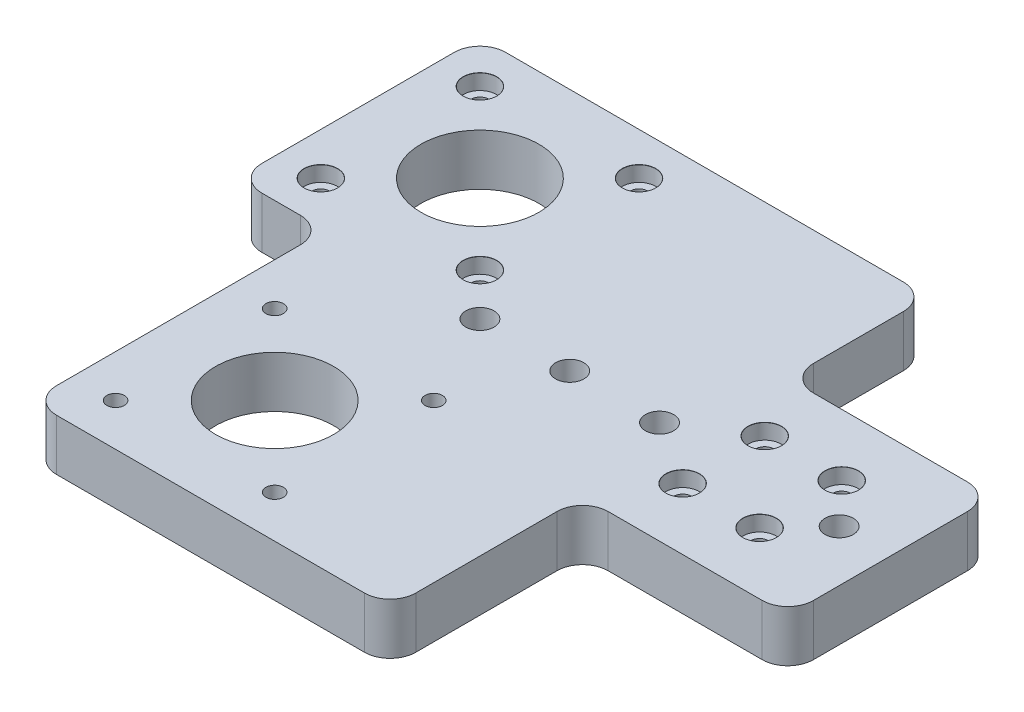
SolidWorks part; units mm, degrees
ref_plane "Front Plane" through (0, 0, 0) normal (0, 0, 1) x (1, 0, 0)
ref_plane "Top Plane" through (0, 0, 0) normal (0, 1, 0) x (1, 0, 0)
ref_plane "Right Plane" through (0, 0, 0) normal (1, 0, 0) x (0, 0, -1)
sketch "Sketch1" plane through (0, 0, 0) normal (0, 1, 0) x (1, 0, 0)
  line L0 (0, 0) -> (110, 0) construction
  line L1 (110, 0) -> (110, 20) construction
  line L2 (110, 20) -> (0, 20) construction
  line L3 (0, 20) -> (0, 0) construction
  line L4 (110, 30) -> (110, -10) construction
  line L5 (110, 30) -> (80, 30) construction
  line L6 (80, 30) -> (80, -10) construction
  line L7 (80, -10) -> (110, -10) construction
  line L8 (0, 67.5) -> (0, -47.5)
  line L16 (0, 67.5) -> (70, 67.5)
  line L18 (0, -47.5) -> (70, -47.5)
  line L19 (70, 67.5) -> (70, 30)
  line L22 (110, -10) -> (70, -10)
  line L23 (70, -10) -> (70, -47.5)
  line L24 (70, 30) -> (110, 30)
  line L25 (110, 30) -> (110, -10)
  point P8 (110, 10)
  point P13 (0, 10)
  dimension "D1" = 20
  dimension "D2" = 37.5
  dimension "D3" = 30
  dimension "D4" = 40
  dimension "D5" = 110
  dimension "D6" = 10
extrude "Boss-Extrude1" add sketch "Sketch1" along normal blind 10
fillet "Fillet1" radius 5 8 edges at (70, 5, -30) (110, 5, -30) (110, 5, 10) (70, 5, 10) (0, 5, 47.5) (0, 5, -67.5) (70, 5, -67.5) (70, 5, 47.5)
sketch "Sketch3" plane through (0, 10, 0) normal (0, 1, 0) x (1, 0, 0)
  line L0 (5, -47.5) -> (65, -47.5) construction
  line L1 (0, 62.5) -> (0, -42.5) construction
  circle A0 centre (23.75, -23.75) radius 11.5
  dimension "D3" = 23
  dimension "D1" = 23.75
  dimension "D2" = 23.75
extrude "Cut-Extrude1" cut sketch "Sketch3" against normal blind 10
sketch "Sketch4" plane through (0, 0, 0) normal (0, -1, 0) x (1, 0, 0)
  line L1 (39.25, 39.25) -> (8.25, 39.25)
  line L2 (39.25, 39.25) -> (39.25, 8.25)
  line L3 (39.25, 8.25) -> (8.25, 8.25)
  line L4 (8.25, 39.25) -> (8.25, 8.25)
  line L5 (39.25, 39.25) -> (8.25, 8.25) construction
  line L6 (39.25, 8.25) -> (8.25, 39.25) construction
  point P0 (23.75, 23.75)
  dimension "D1" = 31
hole_wizard "CBORE for M3 SHCS1" positions "Sketch5" profile "Sketch6" counterbore size "M3" standard "ANSI Metric" end condition through all
sketch "Sketch5" plane through (0, 0, 0) normal (0, -1, 0) x (-1, 0, 0)
  point P0 (-39.25, -8.25)
  point P3 (-8.25, -39.25)
  point P6 (-8.25, -8.25)
  point P9 (-39.25, -39.25)
sketch "Sketch6" plane through (39.25, 0, 8.25) normal (1, 0, 0) x (0, 0, -1)
  line L0 (0, 0) -> (0, 10)
  line L1 (0, 10) -> (1.7, 10)
  line L3 (1.7, 10) -> (1.7, 3)
  line L4 (3.25, 3) -> (1.7, 3)
  line L5 (3.25, 3) -> (3.25, 0.025)
  line L6 (3.25, 0.025) -> (3.275, 0)
  line L7 (3.275, 0) -> (0, 0)
  line L8 (-3.25, 0.025) -> (-3.275, 0) construction
  line L11 (0, -6.35) -> (0, 107.95) construction
  dimension "Thru Hole Dia." = 3.4
  dimension "Thru Hole Depth" = 10
  dimension "C'Bore Dia." = 6.5
  dimension "C'Bore Depth" = 3
  dimension "Near C'Sink Dia." = 6.55
  dimension "Near C'Sink Angle" = 90
sketch "Sketch7" plane through (0, 10, 0) normal (0, 1, 0) x (1, 0, 0)
  line L1 (92.5, 18) -> (77.5, 18)
  line L2 (92.5, 18) -> (92.5, 2)
  line L3 (92.5, 2) -> (77.5, 2)
  line L4 (77.5, 18) -> (77.5, 2)
  line L5 (92.5, 18) -> (77.5, 2) construction
  line L6 (92.5, 2) -> (77.5, 18) construction
  line L7 (110, 10) -> (0, 10)
  line L8 (0, 67.5) -> (0, -47.5) construction
  line L10 (110, 30) -> (110, -10) construction
  point P0 (85, 10)
  dimension "D1" = 15
  dimension "D2" = 16
  dimension "D3" = 25
hole_wizard "CBORE for M3 SHCS2" positions "Sketch8" profile "Sketch9" counterbore size "M3" standard "ANSI Metric" end condition through all
sketch "Sketch8" plane through (0, 10, 0) normal (0, 1, 0) x (1, 0, 0)
  point P0 (77.5, 18)
  point P3 (92.5, 18)
  point P6 (92.5, 2)
  point P9 (77.5, 2)
sketch "Sketch9" plane through (77.5, 10, -18) normal (1, 0, 0) x (0, 0, 1)
  line L0 (0, 0) -> (0, 10)
  line L1 (0, 10) -> (1.7, 10)
  line L3 (1.7, 10) -> (1.7, 3)
  line L4 (3.25, 3) -> (1.7, 3)
  line L5 (3.25, 3) -> (3.25, 0.025)
  line L6 (3.25, 0.025) -> (3.275, 0)
  line L7 (3.275, 0) -> (0, 0)
  line L8 (-3.25, 0.025) -> (-3.275, 0) construction
  line L11 (0, -6.35) -> (0, 107.95) construction
  dimension "Thru Hole Dia." = 3.4
  dimension "Thru Hole Depth" = 10
  dimension "C'Bore Dia." = 6.5
  dimension "C'Bore Depth" = 3
  dimension "Near C'Sink Dia." = 6.55
  dimension "Near C'Sink Angle" = 90
sketch "Sketch10" plane through (0, 0, 0) normal (0, -1, 0) x (1, 0, 0)
  line L0 (110, -10) -> (0, -10) construction
  line L1 (110, 5) -> (110, -25) construction
  line L2 (0, -62.5) -> (0, 42.5) construction
  point P6 (100, -10)
  point P7 (30, -10)
  point P8 (47.5, -10)
  point P9 (65, -10)
  dimension "D1" = 30
  dimension "D2" = 17.5
  dimension "D3" = 17.5
  dimension "D4" = 10
hole_wizard "CBORE for M5 SHCS1" positions "Sketch13" profile "Sketch12" counterbore size "M5" standard "ANSI Metric" end condition through all
sketch "Sketch13" plane through (0, 0, 0) normal (0, -1, 0) x (-1, 0, 0)
  point P0 (-100, 10)
  point P3 (-65, 10)
  point P6 (-47.5, 10)
  point P9 (-30, 10)
sketch "Sketch12" plane through (100, 0, -10) normal (1, 0, 0) x (0, 0, -1)
  line L0 (0, 0) -> (0, 10)
  line L1 (0, 10) -> (2.75, 10)
  line L3 (2.75, 10) -> (2.75, 5)
  line L4 (5, 5) -> (2.75, 5)
  line L5 (5, 5) -> (5, 0.025)
  line L6 (5, 0.025) -> (5.025, 0)
  line L7 (5.025, 0) -> (0, 0)
  line L8 (-5, 0.025) -> (-5.025, 0) construction
  line L11 (0, -6.35) -> (0, 107.95) construction
  dimension "Thru Hole Dia." = 5.5
  dimension "Thru Hole Depth" = 10
  dimension "C'Bore Dia." = 10
  dimension "C'Bore Depth" = 5
  dimension "Near C'Sink Dia." = 10.05
  dimension "Near C'Sink Angle" = 90
sketch "Sketch14" plane through (0, 10, 0) normal (0, 1, 0) x (1, 0, 0)
  line L0 (0, 10) -> (-17.5, 10)
  line L1 (0, 62.5) -> (0, -42.5) construction
  line L2 (-17.5, 10) -> (-17.5, 67.5)
  line L3 (-17.5, 67.5) -> (5, 67.5)
  line L4 (0, 62.5) -> (0, 10)
  arc A0 (5, 67.5) -> (0, 62.5) centre (5, 62.5) ccw construction
  arc A1 (5, 67.5) -> (0, 62.5) centre (5, 62.5) ccw
  dimension "D1" = 17.5
extrude "Boss-Extrude2" add sketch "Sketch14" against normal blind 10
sketch "Sketch15" plane through (0, 10, 0) normal (0, 1, 0) x (1, 0, 0)
  line L0 (-17.5, 67.5) -> (65, 67.5)
  line L1 (-17.5, 67.5) -> (-17.5, 57.5)
  line L2 (-17.5, 67.5) -> (-17.5, 10) construction
  line L3 (-17.5, 57.5) -> (70, 57.5)
  line L5 (70, 35) -> (70, 62.5) construction
  line L6 (70, 57.5) -> (70, 62.5)
  arc A2 (70, 62.5) -> (65, 67.5) centre (65, 62.5) ccw construction
  arc A3 (70, 62.5) -> (65, 67.5) centre (65, 62.5) ccw
  dimension "D1" = 10
extrude "Cut-Extrude2" cut sketch "Sketch15" against normal blind 10
fillet "Fillet2" radius 5 4 edges at (0, 5, -10) (70, 5, -57.5) (-17.5, 5, -57.5) (-17.5, 5, -10)
sketch "Sketch16" plane through (0, 10, 0) normal (0, 1, 0) x (1, 0, 0)
  line L0 (-12.5, 57.5) -> (65, 57.5) construction
  line L1 (-17.5, 52.5) -> (-17.5, 15) construction
  circle A0 centre (6.25, 33.75) radius 11.5
  dimension "D1" = 23
  dimension "D2" = 23.75
  dimension "D3" = 23.75
extrude "Cut-Extrude3" cut sketch "Sketch16" against normal through all
sketch "Sketch17" plane through (0, 10, 0) normal (0, 1, 0) x (1, 0, 0)
  line L1 (21.75, 49.25) -> (-9.25, 49.25)
  line L2 (21.75, 49.25) -> (21.75, 18.25)
  line L3 (21.75, 18.25) -> (-9.25, 18.25)
  line L4 (-9.25, 49.25) -> (-9.25, 18.25)
  line L5 (21.75, 49.25) -> (-9.25, 18.25) construction
  line L6 (21.75, 18.25) -> (-9.25, 49.25) construction
  point P0 (6.25, 33.75)
  dimension "D1" = 31
hole_wizard "CBORE for M3 SHCS3" positions "Sketch18" profile "Sketch19" counterbore size "M3" standard "ANSI Metric" end condition through all
sketch "Sketch18" plane through (0, 10, 0) normal (0, 1, 0) x (1, 0, 0)
  point P0 (-9.25, 49.25)
  point P3 (21.75, 49.25)
  point P6 (21.75, 18.25)
  point P9 (-9.25, 18.25)
sketch "Sketch19" plane through (-9.25, 10, -49.25) normal (1, 0, 0) x (0, 0, 1)
  line L0 (0, 0) -> (0, 10)
  line L1 (0, 10) -> (1.7, 10)
  line L3 (1.7, 10) -> (1.7, 3)
  line L4 (3.25, 3) -> (1.7, 3)
  line L5 (3.25, 3) -> (3.25, 0.025)
  line L6 (3.25, 0.025) -> (3.275, 0)
  line L7 (3.275, 0) -> (0, 0)
  line L8 (-3.25, 0.025) -> (-3.275, 0) construction
  line L11 (0, -6.35) -> (0, 107.95) construction
  dimension "Thru Hole Dia." = 3.4
  dimension "Thru Hole Depth" = 10
  dimension "C'Bore Dia." = 6.5
  dimension "C'Bore Depth" = 3
  dimension "Near C'Sink Dia." = 6.55
  dimension "Near C'Sink Angle" = 90
